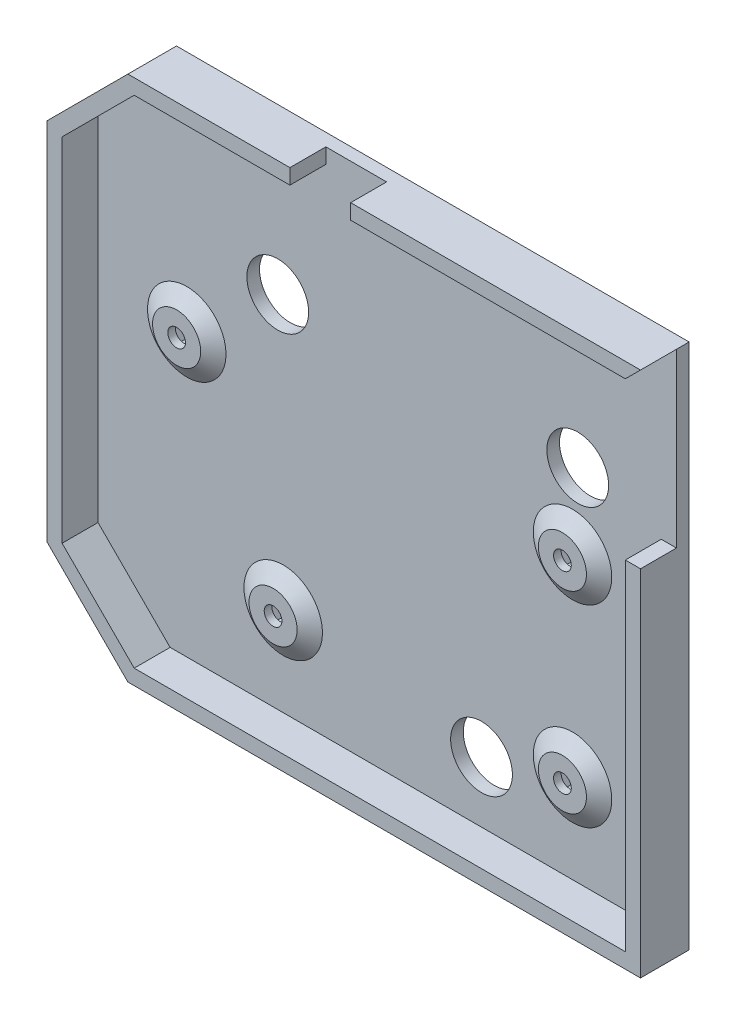
SolidWorks part; units mm, degrees
material "Delrin 2700 NC010, copolymère d'acétal à faible viscosité (SS)"
ref_plane "Plan de face" through (0, 0, 0) normal (0, 0, 1) x (1, 0, 0)
ref_plane "Plan de dessus" through (0, 0, 0) normal (0, 1, 0) x (1, 0, 0)
ref_plane "Plan de droite" through (0, 0, 0) normal (1, 0, 0) x (0, 0, -1)
sketch "Esquisse1" plane through (0, 0, 0) normal (0, 0, 1) x (1, 0, 0)
  line L0 (0, -85) -> (16, -101)
  line L4 (117.25, 3) -> (117.25, -101)
  line L5 (16, 3) -> (0, -13)
  line L7 (117.25, 3) -> (16, 3)
  line L8 (0, -13) -> (0, -85)
  line L9 (16, -101) -> (117.25, -101)
  dimension "D1" = 104
  dimension "D2" = 117.25
  dimension "D3" = 16
  dimension "D4" = 16
  dimension "D5" = 16
  dimension "D6" = 16
extrude "Boss.-Extru.1" add sketch "Esquisse1" along normal blind 2.5
sketch "Esquisse2" plane through (0, 0, 2.5) normal (0, 0, 1) x (1, 0, 0)
  line L0 (0, -13) -> (0, -85) construction
  line L1 (3, 0) -> (114.25, 0) construction
  line L2 (3, 0) -> (3, -98) construction
  line L3 (3, -98) -> (114.25, -98) construction
  line L4 (114.25, 0) -> (114.25, -98) construction
  line L5 (16, -101) -> (117.25, -101) construction
  line L6 (117.25, -101) -> (117.25, 3) construction
  line L7 (117.25, 3) -> (16, 3) construction
  line L8 (114.25, -31) -> (117.25, -31)
  line L9 (3, -83.7574) -> (17.2426, -98)
  line L10 (0, -85) -> (16, -101) construction
  line L11 (3, -14.2426) -> (17.2426, 0)
  line L12 (16, 3) -> (0, -13) construction
  line L14 (3, -14.2426) -> (3, -83.7574)
  line L15 (17.2426, -98) -> (114.25, -98)
  line L16 (117.25, 3) -> (117.25, -101) construction
  line L17 (117.25, -101) -> (16, -101)
  line L18 (16, -101) -> (0, -85)
  line L19 (0, -85) -> (0, -13)
  line L20 (0, -13) -> (16, 3)
  line L22 (114.25, 0) -> (117.25, 3)
  line L23 (114.25, -98) -> (114.25, -31)
  line L24 (117.25, -31) -> (117.25, -101)
  line L25 (48, 0) -> (48, 3)
  line L26 (60, 0) -> (60, 3)
  line L27 (17.2426, 0) -> (48, 0)
  line L28 (48, 3) -> (16, 3)
  line L29 (60, 3) -> (117.25, 3)
  line L30 (114.25, 0) -> (60, 0)
  point P33 (48, 0)
  point P34 (60, 0)
  dimension "D1" = 3
  dimension "D2" = 3
  dimension "D3" = 3
  dimension "D4" = 3
  dimension "D5" = 3
  dimension "D6" = 3
  dimension "D7" = 70
  dimension "D8" = 45
  dimension "D9" = 12
extrude "Boss.-Extru.2" add sketch "Esquisse2" along normal blind 7.1
sketch "Esquisse3" plane through (0, 0, 2.5) normal (0, 0, 1) x (1, 0, 0)
  line L0 (114.25, -31) -> (114.25, -98) construction
  line L2 (3, -83.7574) -> (3, -14.2426) construction
  line L3 (114.25, -31) -> (114.25, -98) construction
  line L4 (114.25, -98) -> (17.2426, -98) construction
  line L5 (60, 3) -> (48, 3) construction
  circle A0 centre (97.75, -27) radius 6.1
  circle A1 centre (38.5, -27) radius 6.1
  circle A2 centre (78.75, -86) radius 6.1
  dimension "D1" = 16.5
  dimension "D2" = 30
  dimension "D3" = 30
  dimension "D4" = 35.5
  dimension "D5" = 35.5
  dimension "D6" = 12
extrude "Enlèv. mat.-Extru.1" cut sketch "Esquisse3" against normal blind 10
sketch "Esquisse5" plane through (0, 0, 2.5) normal (0, 0, 1) x (1, 0, 0)
  line L0 (114.25, -98) -> (17.2426, -98) construction
  line L1 (114.25, -31) -> (114.25, -98) construction
  point P0 (20.525, -42.37)
  point P1 (96.725, -42.37)
  point P2 (96.725, -80.47)
  point P3 (39.575, -80.47)
  dimension "D1" = 38.1
  dimension "D2" = 17.53
  dimension "D3" = 17.525
  dimension "D4" = 76.2
  dimension "D5" = 57.15
ref_axis "Axe5" through (20.525, -42.37, 2.5) along (0, 0, 1)
ref_axis "Axe6" through (96.725, -42.37, 2.5) along (0, 0, 1)
ref_axis "Axe7" through (39.575, -80.47, 2.5) along (0, 0, 1)
ref_axis "Axe8" through (96.725, -80.47, 2.5) along (0, 0, 1)
sketch3d "Esquisse3D5"
  line L0 (20.525, -42.37, 2.5) -> (96.725, -42.37, 2.5) construction
  line L1 (39.575, -80.47, 2.5) -> (96.725, -80.47, 2.5) construction
ref_plane "Plan4" through (96.725, -42.37, 2.5) normal (1, 0, 0) x (0, 0, -1)
sketch "Esquisse8" plane through (96.725, -42.37, 2.5) normal (1, 0, 0) x (0, 0, -1)
  line L0 (0, 1.75) -> (0, 7.75)
  line L1 (0, 7.75) -> (-2, 4.75)
  line L2 (-2, 4.75) -> (-2, 1.75)
  line L3 (-2, 1.75) -> (0, 1.75)
  line L5 (0, 0) -> (-50.5083, 0) construction
  point P0 (0, 1.75)
  dimension "D1" = 6
  dimension "D2" = 3
  dimension "D3" = 2
  dimension "D4" = 1.75
revolve "Révolution3" add sketch "Esquisse8" angle 360 about axis through (96.725, -42.37, 2.5) along (0, 0, 1)
ref_plane "Plan5" through (39.575, -80.47, 2.5) normal (1, 0, 0) x (0, 0, -1)
sketch "Esquisse9" plane through (39.575, -80.47, 2.5) normal (1, 0, 0) x (0, 0, -1)
  line L0 (0, 1.75) -> (0, 7.75)
  line L1 (0, 7.75) -> (-2, 4.75)
  line L2 (-2, 4.75) -> (-2, 1.75)
  line L3 (-2, 1.75) -> (0, 1.75)
  point P0 (0, 1.75)
  dimension "D1" = 2
  dimension "D2" = 6
  dimension "D3" = 3
  dimension "D4" = 1.75
revolve "Révolution4" add sketch "Esquisse9" angle 360 about axis through (39.575, -80.47, 2.5) along (0, 0, 1)
ref_plane "Plan6" through (96.725, -80.47, 2.5) normal (1, 0, 0) x (0, 0, -1)
sketch "Esquisse10" plane through (96.725, -80.47, 2.5) normal (1, 0, 0) x (0, 0, -1)
  line L0 (0, 1.75) -> (0, 7.75)
  line L1 (0, 7.75) -> (-2, 4.75)
  line L2 (-2, 4.75) -> (-2, 1.75)
  line L3 (-2, 1.75) -> (0, 1.75)
  point P0 (0, 1.75)
  dimension "D1" = 6
  dimension "D2" = 2
  dimension "D3" = 3
  dimension "D4" = 1.75
revolve "Révolution5" add sketch "Esquisse10" angle 360 about axis through (96.725, -80.47, 2.5) along (0, 0, 1)
hole_wizard "Dégagement M32" positions "Esquisse15" profile "Esquisse16" hole size "M3" standard "Ansi Metric" end condition up to next
sketch "Esquisse15" plane through (0, 0, 2.5) normal (0, 0, 1) x (1, 0, 0)
  point P0 (20.525, -42.37)
  point P3 (39.575, -80.47)
  point P6 (96.725, -42.37)
  point P9 (96.725, -80.47)
sketch "Esquisse16" plane through (20.525, -42.37, 2.5) normal (1, 0, 0) x (0, -1, 0)
  line L0 (0, 0) -> (0, 2.5)
  line L1 (0, 2.5) -> (1.8, 2.5)
  line L2 (1.8, 2.5) -> (1.8, 0)
  line L5 (1.8, 0) -> (0, 0)
  line L11 (0, -6.35) -> (0, 107.95) construction
  dimension "Diamètre du perçage jusqu'au prochain" = 3.6
  dimension "Profondeur du perçage jusqu'au prochain" = 2.5
ref_plane "Plan7" through (20.525, -42.37, 2.5) normal (1, 0, 0) x (0, 0, -1)
sketch "Esquisse17" plane through (20.525, -42.37, 2.5) normal (1, 0, 0) x (0, 0, -1)
  line L1 (0, 1.75) -> (0, 7.75)
  line L2 (0, 7.75) -> (-2, 4.75)
  line L3 (-2, 4.75) -> (-2, 1.75)
  line L4 (-2, 1.75) -> (0, 1.75)
  line L5 (0, 0) -> (-50.3226, 0) construction
  dimension "D1" = 1.75
  dimension "D2" = 6
  dimension "D3" = 3
  dimension "D4" = 2
revolve "Révolution6" add sketch "Esquisse17" angle 360 about axis through (20.525, -42.37, 2.5) along (0, 0, 1)
ref_point "Point1"
ref_point "Point2"
ref_point "Point3"
ref_point "Point4"
sketch "Esquisse18" plane through (0, 0, 0) normal (0, 0, -1) x (-1, 0, 0)
  line L1 (-95.1662, -77.77) -> (-98.2838, -77.77)
  line L2 (-98.2838, -77.77) -> (-99.8427, -80.47)
  line L3 (-99.8427, -80.47) -> (-98.2838, -83.17)
  line L4 (-98.2838, -83.17) -> (-95.1662, -83.17)
  line L5 (-95.1662, -83.17) -> (-93.6073, -80.47)
  line L6 (-93.6073, -80.47) -> (-95.1662, -77.77)
  line L7 (-95.1662, -39.67) -> (-98.2838, -39.67)
  line L8 (-98.2838, -39.67) -> (-99.8427, -42.37)
  line L9 (-99.8427, -42.37) -> (-98.2838, -45.07)
  line L10 (-98.2838, -45.07) -> (-95.1662, -45.07)
  line L11 (-95.1662, -45.07) -> (-93.6073, -42.37)
  line L12 (-93.6073, -42.37) -> (-95.1662, -39.67)
  line L13 (-17.4073, -42.37) -> (-18.9662, -39.67)
  line L14 (-18.9662, -39.67) -> (-22.0838, -39.67)
  line L15 (-22.0838, -39.67) -> (-23.6427, -42.37)
  line L16 (-23.6427, -42.37) -> (-22.0838, -45.07)
  line L17 (-22.0838, -45.07) -> (-18.9662, -45.07)
  line L18 (-18.9662, -45.07) -> (-17.4073, -42.37)
  line L19 (-36.4573, -80.47) -> (-38.0162, -77.77)
  line L20 (-38.0162, -77.77) -> (-41.1338, -77.77)
  line L21 (-41.1338, -77.77) -> (-42.6927, -80.47)
  line L22 (-42.6927, -80.47) -> (-41.1338, -83.17)
  line L23 (-41.1338, -83.17) -> (-38.0162, -83.17)
  line L24 (-38.0162, -83.17) -> (-36.4573, -80.47)
  line L26 (-16, -101) -> (-117.25, -101) construction
  circle A0 centre (-96.725, -80.47) radius 2.7 construction
  circle A1 centre (-96.725, -42.37) radius 2.7 construction
  circle A2 centre (-20.525, -42.37) radius 2.7 construction
  circle A3 centre (-39.575, -80.47) radius 2.7 construction
  dimension "D1" = 5.4
  dimension "D2" = 5.4
  dimension "D3" = 5.4
  dimension "D4" = 5.4
extrude "Enlèv. mat.-Extru.2" cut sketch "Esquisse18" against normal blind 3
